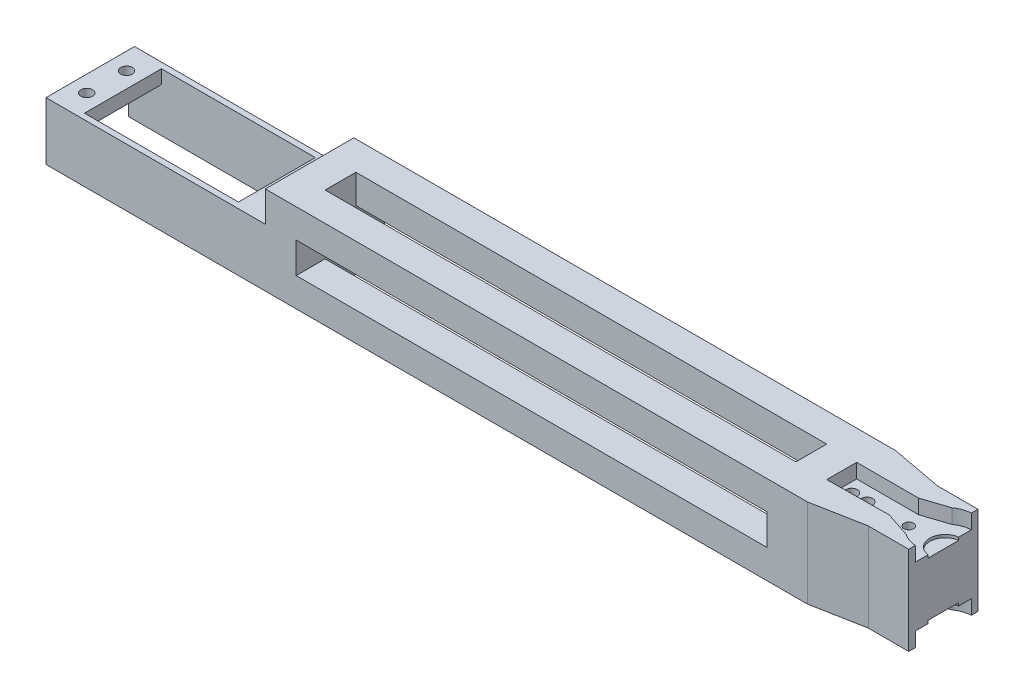
SolidWorks part; units mm, degrees
ref_plane "Front Plane" through (0, 0, 0) normal (0, 0, 1) x (1, 0, 0)
ref_plane "Top Plane" through (0, 0, 0) normal (0, 1, 0) x (1, 0, 0)
ref_plane "Right Plane" through (0, 0, 0) normal (1, 0, 0) x (0, 0, -1)
sketch "Sketch1" plane through (0, 0, 0) normal (0, 1, 0) x (1, 0, 0)
  line L0 (0, 0) -> (14.6038, 0) construction
  line L1 (14.6038, 0) -> (-20.0982, 0) construction
  line L2 (14.6038, -7.2) -> (14.6038, 7.2) construction
  line L3 (-661.2792, -270.937) -> (-113.9458, -270.937) construction
  line L4 (3.082, 5.9567) -> (3.082, -8.253) construction
  line L5 (-17.0385, 7.2) -> (-17.0385, 4.8714) construction
  line L6 (-13.0385, 7.2) -> (-13.0385, 4.8714) construction
  line L7 (6.8243, 9.0002) -> (6.8243, -9.0002)
  line L8 (6.8276, 9.1929) -> (-2.1724, 9.1929) construction
  line L9 (-24.868, 11.5) -> (-24.868, -11.5)
  line L10 (-3.4224, -3.8) -> (-3.4224, 3.8) construction
  line L11 (6.8243, 0.0002) -> (6.8243, 9.0002) construction
  line L12 (6.8243, 0.0002) -> (6.8243, -9.0002) construction
  line L15 (-3.4224, 3.8) -> (3.082, 5.9567)
  line L16 (-3.4224, -3.8) -> (3.082, -5.9567)
  line L17 (-3.4224, 3.8) -> (-19.5134, 3.8)
  line L18 (-19.5134, 3.8) -> (-19.5134, -3.9825)
  line L19 (-17.0385, 11.5) -> (-24.868, 11.5)
  line L20 (-19.5134, -3.9825) -> (-3.4224, -3.8)
  line L21 (6.8243, 9.0002) -> (-3.6905, 9.0002)
  line L22 (6.8243, -9.0002) -> (-3.6905, -9.0002)
  line L23 (-17.0385, -11.5) -> (-17.0385, 11.5) construction
  line L27 (-3.6905, 9.0002) -> (-17.0385, 11.5)
  line L28 (-3.6905, -9.0002) -> (-17.0385, -11.5)
  line L30 (-24.868, -11.5) -> (-17.0385, -11.5)
  arc A0 (6.8243, 3.9714) -> (6.8243, -3.9714) centre (7.3019, 0) ccw
  circle A1 centre (-17.0385, 0) radius 1.5
  circle A2 centre (-13.0385, 0) radius 1.5
  circle A3 centre (-2.1724, 0) radius 1.25
  arc A4 (6.8243, 7.2844) -> (3.082, 5.9567) centre (7.3019, 0) ccw
  arc A5 (3.082, -5.9567) -> (6.8243, -7.2844) centre (7.3019, 0) ccw
  point P8 (0, 0)
  point P17 (-17.0385, 6.0357)
  point P25 (3.082, -5.9567)
  point P26 (0, 0)
  point P35 (-17.0772, 11.5)
  point P41 (-3.4224, 0)
  point P43 (0, 0)
  point P44 (6.826, 0)
  dimension "D4" = 8
  dimension "D5" = 3
  dimension "D7" = 3
  dimension "D10" = 2.5
  dimension "D11" = 14.6
  dimension "D2" = 14.4
  dimension "D6" = 4
  dimension "D8" = 9
  dimension "D12" = 9
  dimension "D13" = 3.8
extrude "Boss-Extrude1" add sketch "Sketch1" along normal mid plane 23 contours A5 L16 L20 L18 L17 L15 A4 L7 L21 L27 L19 L9 L30 L28 L22 region at (6.4327, 0, -8.1423)
extrude "Boss-Extrude2" add sketch "Sketch1<13>" along normal mid plane 15.5 contours L16 A5 L7 A0 A4 L15 L17 L18 L20 A3 A2 A1 region at (-5.3254, 0, 0.0287)
sketch "Sketch1<13>" plane through (0, 0, 0) normal (0, 1, 0) x (1, 0, 0) same geometry as "Sketch1"
extrude "Boss-Extrude3" add sketch "Sketch1<14>" along normal mid plane 14 contours L7 A0 region at (5.3434, 0, 0)
sketch "Sketch1<14>" plane through (0, 0, 0) normal (0, 1, 0) x (1, 0, 0) same geometry as "Sketch1"
sketch "Sketch2" plane through (-24.868, 0, 0) normal (-1, 0, 0) x (0, 0, 1)
  line L1 (-11.5, -11.5) -> (11.5, -11.5)
  line L2 (-11.5, -11.5) -> (-11.5, 11.5)
  line L3 (-11.5, 11.5) -> (11.5, 11.5)
  line L4 (11.5, -11.5) -> (11.5, 11.5)
extrude "Boss-Extrude4" add sketch "Sketch2" along normal blind 190
sketch "Sketch3" plane through (0, 11.5, 0) normal (0, 1, 0) x (1, 0, 0)
  line L0 (-19.5134, -0.0913) -> (-214.868, 0) construction
  line L1 (-19.5134, 3.8) -> (-19.5134, -3.9825) construction
  line L2 (-214.868, -11.5) -> (-214.868, 11.5) construction
  point P6 (0, 0)
sketch "Sketch4" plane through (-214.868, 0, 0) normal (-1, 0, 0) x (0, 0, 1)
  line L0 (0.0456, 11.5) -> (0, -11.5) construction
  line L1 (0.0913, 11.5) -> (0, 11.5) construction
  line L2 (-11.5, -11.5) -> (11.5, -11.5) construction
  line L3 (11.5, 0) -> (-11.5, 0) construction
  line L4 (11.5, -11.5) -> (11.5, 11.5) construction
  line L5 (-11.5, 11.5) -> (-11.5, -11.5) construction
sketch "Sketch5" plane through (0, 0, 11.5) normal (0, 0, 1) x (1, 0, 0)
  line L0 (-214.868, 0) -> (-17.0385, 0) construction
  line L1 (-214.868, 11.5) -> (-214.868, -11.5) construction
  line L2 (-17.0385, 11.5) -> (-17.0385, -11.5) construction
sketch "Sketch8" plane through (0, -11.5, 0) normal (0, -1, 0) x (1, 0, 0)
  line L0 (-214.868, 11.5) -> (-160.868, 11.5) construction
  line L1 (-214.868, 11.5) -> (-17.0385, 11.5) construction
  line L2 (-214.868, 11.5) -> (-214.868, 10) construction
  line L3 (-214.868, 11.5) -> (-214.868, -11.5) construction
  line L4 (-19.5134, 0.0913) -> (-157.8666, 0.0266) construction
  line L5 (-214.8572, -11.5) -> (-214.8586, -10) construction
  line L6 (-157.8666, 10) -> (-166.3666, 10) construction
  line L7 (-206.368, 10) -> (-157.8666, 10) construction
  line L8 (-214.868, 10) -> (-214.8586, -10) construction
  line L9 (-214.8586, -10) -> (-157.8666, -10) construction
  line L10 (-157.8666, 10) -> (-157.8666, -10) construction
  line L11 (-214.868, 10) -> (-206.368, 10) construction
  line L12 (-214.868, 10) -> (-214.868, -10) construction
  line L13 (-214.868, -10) -> (-206.368, -10) construction
  line L14 (-206.368, 10) -> (-206.368, -10) construction
  line L15 (-166.3666, 10) -> (-166.3666, -10) construction
  line L16 (-166.3666, -10) -> (-157.8666, -10) construction
  line L17 (-157.8666, -10) -> (-157.8666, 10) construction
  line L18 (-214.8633, 0) -> (-214.868, 0) construction
  line L19 (-166.3666, 0.0227) -> (-166.3673, 0.0227) construction
  line L20 (-206.368, 0.1491) -> (-214.868, 0) construction
  line L21 (-166.3666, 0.0227) -> (-157.8666, 0.0266) construction
  line L22 (-210.618, 0.0746) -> (-210.618, 2.3246) construction
  line L23 (-210.618, 10) -> (-210.618, 8) construction
  line L24 (-210.618, 0.0746) -> (-210.539, -2.174) construction
  line L25 (-210.2698, -9.8448) -> (-210.34, -7.846) construction
  line L26 (-210.618, 2.3246) -> (-210.618, 8) construction
  line L27 (-210.34, -7.846) -> (-210.539, -2.174) construction
  line L28 (-166.3666, 11.5) -> (-166.3666, 10) construction
  line L29 (-166.3666, -11.4753) -> (-166.368, 9.9931) construction
  line L30 (-166.3666, 10) -> (-166.368, 9.9931) construction
  line L31 (-166.3666, 10) -> (-157.8666, 10) construction
  line L32 (-166.3666, 10) -> (-166.3666, -10) construction
  line L33 (-166.3666, -10) -> (-157.8666, -10) construction
  line L34 (-157.8666, 10) -> (-157.8666, -10) construction
  line L35 (-168.3923, 0.0217) -> (-166.3666, 0.0227) construction
  line L36 (-157.8666, -0.0232) -> (-166.3666, 0.0227) construction
  line L37 (-162.1166, -0.0003) -> (-162.1166, 2.2497) construction
  line L38 (-162.1166, 10) -> (-162.1166, 8) construction
  line L39 (-162.1166, -0.0003) -> (-162.1409, -2.2502) construction
  line L40 (-162.2246, -10) -> (-162.203, -8.0001) construction
  line L41 (-162.1166, 2.2497) -> (-162.1166, 8) construction
  line L42 (-162.203, -8.0001) -> (-162.1409, -2.2502) construction
  line L43 (-206.368, 0.1491) -> (-198.868, 0.0075) construction
  line L44 (-157.8666, -10) -> (-214.8572, -10)
  line L45 (-157.8666, -10) -> (-157.8666, -11.5)
  line L46 (-157.8666, -11.5) -> (-214.8572, -11.5)
  line L47 (-214.8572, -10) -> (-214.8572, -11.5)
  line L48 (-157.8666, 10) -> (-214.868, 10)
  line L49 (-157.8666, 10) -> (-157.8666, 11.5)
  line L50 (-157.8666, 11.5) -> (-214.868, 11.5)
  line L51 (-214.868, 10) -> (-214.868, 11.5)
  line L52 (-19.5134, 0.0913) -> (-214.868, 0) construction
  line L53 (-168.3923, 0.0217) -> (-198.868, 0.0075)
  line L55 (-206.368, 10) -> (-166.3666, 10)
  line L56 (-206.368, 10) -> (-206.368, -10)
  line L57 (-206.368, -10) -> (-166.3666, -10)
  line L58 (-166.3666, 10) -> (-166.3666, -10)
  line L59 (-214.868, 10) -> (-206.368, 10)
  line L60 (-214.868, 10) -> (-214.868, -10)
  line L61 (-214.868, -10) -> (-206.368, -10)
  line L62 (-206.368, 10) -> (-206.368, -10)
  line L63 (-166.3666, 10) -> (-157.8666, 10)
  line L64 (-166.3666, 10) -> (-166.3666, -10)
  line L65 (-166.3666, -10) -> (-157.8666, -10)
  line L66 (-157.8666, 10) -> (-157.8666, -10)
  circle A0 centre (-210.618, 5.1623) radius 1.5
  circle A1 centre (-210.4395, -5.01) radius 1.5
  circle A2 centre (-162.1166, 5.1249) radius 1.5
  circle A3 centre (-162.1719, -5.1251) radius 1.5
  line M8 (-214.868, 11.5) -> (-214.868, -11.5)
  dimension "D7" = 3
  dimension "D12" = 3
  dimension "D1" = 54
  dimension "D2" = 1.5
  dimension "D3" = 8.5
  dimension "D4" = 40
  dimension "D5" = 2.25
  dimension "D6" = 2
  dimension "D8" = 1.5
  dimension "D9" = 8.5
  dimension "D10" = 2.25
  dimension "D11" = 2
  dimension "D13" = 7.5
sketch "Sketch9" plane through (-214.868, 0, 0) normal (-1, 0, 0) x (0, 0, 1)
  line L0 (11.5, 0) -> (11.5, 3.5) construction
  line L1 (11.5, -11.5) -> (11.5, 11.5) construction
  line L2 (0, -11.5) -> (0.0456, 11.5) construction
  line L3 (11.5, 3.5) -> (-11.5, 3.5) construction
  line L4 (11.5, 3.5) -> (11.5, -11.5) construction
  line L5 (11.5, -11.5) -> (-11.5, -11.5) construction
  line L6 (-11.5, 3.5) -> (-11.5, -11.5) construction
  line L7 (11.5, 3.5) -> (10, 3.5)
  line L9 (11.5, -11.5) -> (10, -11.5)
  line L10 (10, 0) -> (10, -11.5)
  line L11 (-11.4999, -11.4544) -> (-9.9999, -11.4603)
  line L12 (-9.9404, 3.5396) -> (-9.9406, 3.5)
  line L13 (-12.1123, 3.5455) -> (-9.9404, 3.5396)
  line L15 (11.5, 0) -> (-11.5, 0) construction
  line L16 (11.5, 3.5) -> (-11.5, 3.5)
  line L17 (11.5, 3.5) -> (11.5, 0)
  line L19 (-11.5, 3.5) -> (-11.5, 0)
  line L20 (-9.9544, 0) -> (-9.9999, -11.4603)
  line L21 (11.5, 0) -> (-11.5, 0)
  line L22 (11.5, 11.5) -> (-12.1123, 11.5)
  line L23 (11.5, 11.5) -> (11.5, 3.5455)
  line L24 (11.5, 3.5455) -> (-12.1123, 3.5455)
  line L25 (-12.1123, 11.5) -> (-12.1123, 3.5455)
  line L26 (11.5, -11.5) -> (10, -11.5)
  line L29 (-11.5, 0) -> (-11.4999, -11.4544)
  line L30 (11.5, 0) -> (11.5, -11.5)
  point P7 (-11.4404, 11.5)
  point P23 (-11.5, 0)
  point P28 (0, 0)
  line M25 (11.5, -11.5) -> (11.5, 11.5)
  line M26 (11.5, 11.5) -> (-11.5, 11.5)
  dimension "D1" = 3.5
  dimension "D2" = 1.5
  dimension "D3" = 1.5
extrude "Cut-Extrude1" cut sketch "Sketch9" against normal blind 57 contours L25 L24 M26 M25 region at (-214.868, 7.5228, -0.3062)
extrude "Cut-Extrude5" cut sketch "Sketch8" against normal blind 11.5 contours L61 L44 L56 L48 A0 A1 M8 | L66 L48 L58 L44 A2 A3 | A3 | A2 | L58 L48 L56 L44 | A0 | A1 region at (-162.1141, -11.5, 0) region at (-186.3673, -11.5, 0) region at (-210.6261, -11.5, -0.0069) region at (-210.618, -11.5, 5.1623) region at (-210.4395, -11.5, -5.01) region at (-162.1166, -11.5, 5.1249) region at (-162.1719, -11.5, -5.1251)
extrude "Cut-Extrude7" cut sketch "Sketch8<6>" against normal blind 15.55 contours A1 | A0 | A2 | A3 | L58 L48 L56 L44 region at (-186.3673, -11.5, 0) region at (-210.618, -11.5, 5.1623) region at (-210.4395, -11.5, -5.01) region at (-162.1166, -11.5, 5.1249) region at (-162.1719, -11.5, -5.1251)
sketch "Sketch8<6>" plane through (0, -11.5, 0) normal (0, -1, 0) x (1, 0, 0) same geometry as "Sketch8"
sketch "Sketch10" plane through (0, 11.5, 0) normal (0, 1, 0) x (1, 0, 0)
  line L0 (-149.8595, -3.9825) -> (-157.8595, -3.9825) construction
  line L1 (-19.5134, -3.9825) -> (-27.5134, -3.9825) construction
  line L2 (-19.5134, -3.9825) -> (-19.5134, 4.0175) construction
  line L3 (-19.5134, 4.0175) -> (-27.5134, 4.0175) construction
  line L4 (-27.5134, -3.9825) -> (-27.5134, 4.0175) construction
  line L5 (-149.8595, -3.9825) -> (-149.8595, 4.0175) construction
  line L6 (-149.8595, 4.0175) -> (-157.8595, 4.0175) construction
  line L7 (-157.8595, -3.9825) -> (-157.8595, 4.0175) construction
  line L8 (-27.5134, -3.9825) -> (-27.5134, -11.5) construction
  line L9 (-27.5134, -3.9825) -> (-149.8595, -3.9825)
  line L10 (-27.5134, -3.9825) -> (-27.5134, 4.0175)
  line L11 (-27.5134, 4.0175) -> (-149.8595, 4.0175)
  line L12 (-149.8595, -3.9825) -> (-149.8595, 4.0175)
  line L13 (-157.868, -11.5) -> (-17.0385, -11.5) construction
  line L14 (-149.8595, -3.9825) -> (-149.8595, -11.5) construction
  point P9 (0, 0)
  dimension "D1" = 8
  dimension "D2" = 8
  dimension "D3" = 8
  dimension "D4" = 8
sketch "Sketch11" plane through (0, 0, 11.5) normal (0, 0, 1) x (1, 0, 0)
  line L0 (-27.5134, 11.5) -> (-27.5134, -11.5) construction
  line L1 (-214.868, -11.5) -> (-17.0385, -11.5) construction
  line L2 (-149.8595, 11.5) -> (-149.8595, -11.5) construction
  line L3 (-27.5134, 4) -> (-27.5134, -4)
  line L4 (-27.5134, 0) -> (-149.8595, 0) construction
  line L5 (-149.8595, 4) -> (-149.8595, -4)
  line L6 (-27.5134, -4) -> (-149.8595, -4)
  line L7 (-27.5134, 4) -> (-149.8595, 4)
  dimension "D1" = 4
  dimension "D2" = 4
extrude "Cut-Extrude8" cut sketch "Sketch11" against normal blind 85.55
extrude "Cut-Extrude9" cut sketch "Sketch10" against normal blind 105.55
